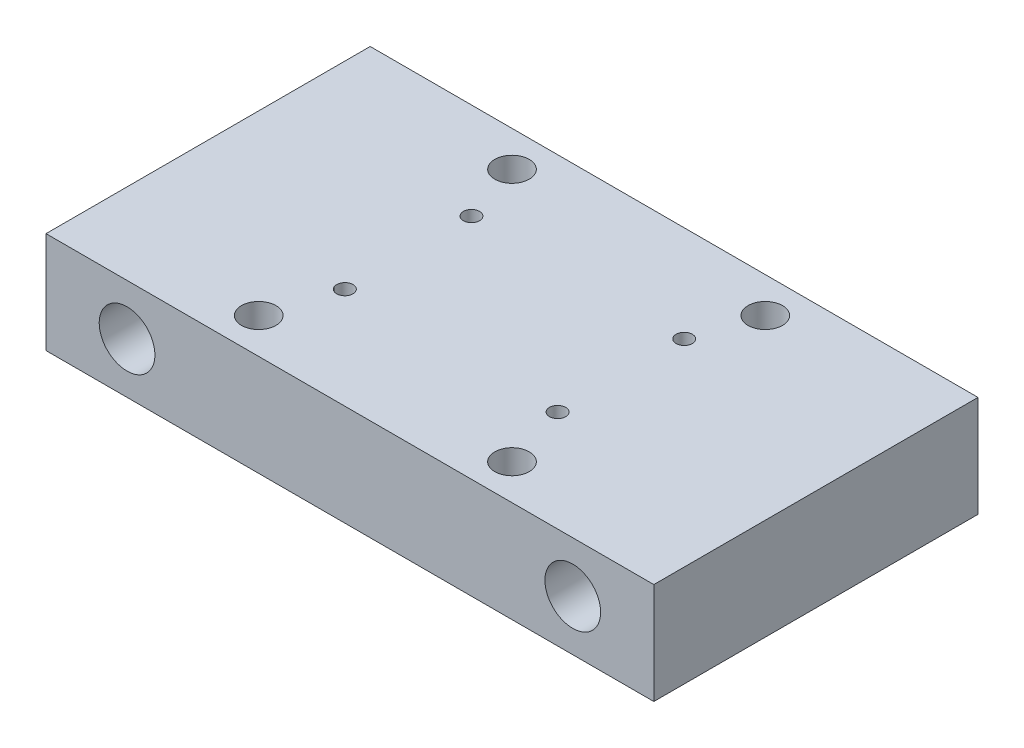
SolidWorks part; units mm, degrees
ref_plane "Front Plane" through (0, 0, 0) normal (0, 0, 1) x (1, 0, 0)
ref_plane "Top Plane" through (0, 0, 0) normal (0, 1, 0) x (1, 0, 0)
ref_plane "Right Plane" through (0, 0, 0) normal (1, 0, 0) x (0, 0, -1)
sketch "Sketch1" plane through (0, 0, 0) normal (0, 1, 0) x (1, 0, 0)
  line L1 (-12.5, 12.5) -> (12.5, 12.5)
  line L2 (-12.5, 12.5) -> (-12.5, -12.5)
  line L3 (-12.5, -12.5) -> (12.5, -12.5)
  line L4 (12.5, 12.5) -> (12.5, -12.5)
  line L5 (-12.5, 12.5) -> (12.5, -12.5) construction
  line L6 (-12.5, -12.5) -> (12.5, 12.5) construction
  line L7 (-30, 16) -> (30, 16)
  line L8 (-30, 16) -> (-30, -16)
  line L9 (-30, -16) -> (30, -16)
  line L10 (30, 16) -> (30, -16)
  line L11 (-30, 16) -> (30, -16) construction
  line L12 (-30, -16) -> (30, 16) construction
  point P0 (0, 0)
  point P6 (0, 0)
  dimension "D1" = 25
  dimension "D2" = 32
  dimension "D3" = 60
sketch "Sketch2" plane through (0, 0, 0) normal (0, 1, 0) x (1, 0, 0)
  line L0 (-30, 16) -> (30, 16) construction
  line L1 (30, 16) -> (30, -16) construction
  line L2 (-30, -16) -> (30, -16) construction
  line L3 (-30, 16) -> (-30, -16) construction
  line L4 (-30, 16) -> (30, 16)
  line L5 (30, 16) -> (30, -16)
  line L6 (-30, -16) -> (30, -16)
  line L7 (-30, 16) -> (-30, -16)
extrude "Boss-Extrude1" add sketch "Sketch2" along normal blind 10
hole_wizard "CBORE for M3 SHCS1" positions "Sketch3" profile "Sketch4" counterbore size "M3" standard "ANSI Metric" end condition through all
sketch "Sketch3" plane through (0, 0, 0) normal (0, -1, 0) x (-1, 0, 0)
  point P0 (12.5, 12.5)
  point P2 (12.5, -12.5)
  point P5 (-12.5, -12.5)
  point P8 (-12.5, 12.5)
sketch "Sketch4" plane through (-12.5, 0, -12.5) normal (1, 0, 0) x (0, 0, -1)
  line L0 (0, 0) -> (0, 10)
  line L1 (0, 10) -> (1.7, 10)
  line L3 (1.7, 10) -> (1.7, 5)
  line L4 (1.7, 5) -> (3.25, 5)
  line L5 (3.25, 5) -> (3.25, 0)
  line L7 (3.25, 0) -> (0, 0)
  line L11 (0, -6.35) -> (0, 107.95) construction
  dimension "Thru Hole Dia." = 3.4
  dimension "Thru Hole Depth" = 10
  dimension "C'Bore Dia." = 6.5
  dimension "C'Bore Depth" = 5
sketch "Sketch6" plane through (0, 0, 0) normal (0, -1, 0) x (-1, 0, 0)
  line L1 (8.5, 4) -> (-8.5, 4)
  line L2 (8.5, 4) -> (8.5, 16)
  line L3 (8.5, 16) -> (-8.5, 16)
  line L4 (-8.5, 4) -> (-8.5, 16)
  line L5 (30, 16) -> (-30, 16) construction
  line L6 (0, 0) -> (0, 4) construction
  point P4 (8.5, 3.216)
  dimension "D1" = 17
  dimension "D2" = 12
extrude "Cut-Extrude2" cut sketch "Sketch6" against normal blind 2
sketch "Sketch8" plane through (0, 0, -16) normal (0, 0, -1) x (-1, 0, 0)
  line L0 (30, 5) -> (-30, 5) construction
  line L1 (30, 10) -> (30, 0) construction
  line L2 (-30, 10) -> (-30, 0) construction
  line L4 (17.2657, 5) -> (19.6329, 0.9)
  line L5 (19.6329, 0.9) -> (24.3671, 0.9)
  line L6 (24.3671, 0.9) -> (26.7343, 5)
  line L7 (26.7343, 5) -> (24.3671, 9.1)
  line L8 (24.3671, 9.1) -> (19.6329, 9.1)
  line L9 (19.6329, 9.1) -> (17.2657, 5)
  line L10 (-17.2657, 5) -> (-19.6329, 9.1)
  line L11 (-19.6329, 9.1) -> (-24.3671, 9.1)
  line L12 (-24.3671, 9.1) -> (-26.7343, 5)
  line L13 (-26.7343, 5) -> (-24.3671, 0.9)
  line L14 (-24.3671, 0.9) -> (-19.6329, 0.9)
  line L15 (-19.6329, 0.9) -> (-17.2657, 5)
  circle A0 centre (22, 5) radius 4.1 construction
  circle A1 centre (-22, 5) radius 4.1 construction
  dimension "D1" = 8.2
  dimension "D2" = 8
  dimension "D3" = 8
extrude "Cut-Extrude4" cut sketch "Sketch8" against normal blind 5
hole_wizard "M5 Clearance Hole1" positions "Sketch10" profile "Sketch11" hole size "M5" standard "ANSI Metric" end condition through all
sketch "Sketch10" plane through (0, 0, -11) normal (0, 0, -1) x (-1, 0, 0)
  line L0 (19.6329, 0.9) -> (24.3671, 9.1)
  line L2 (-19.6329, 9.1) -> (-24.3671, 0.9)
  point P0 (22, 5)
  point P2 (-22, 5)
sketch "Sketch11" plane through (-22, 5, -11) normal (1, 0, 0) x (0, 1, 0)
  line L0 (0, 0) -> (0, 27)
  line L1 (0, 27) -> (2.75, 27)
  line L2 (2.75, 27) -> (2.75, 0)
  line L5 (2.75, 0) -> (0, 0)
  line L11 (0, -6.35) -> (0, 107.95) construction
  dimension "Thru Hole Dia." = 5.5
  dimension "Thru Hole Depth" = 27
sketch "Sketch12" plane through (0, 0, 0) normal (0, -1, 0) x (1, 0, 0)
  line L0 (-8.5, -16) -> (-30, -16) construction
  line L1 (12.5, -16) -> (-12.5, -16) construction
  line L2 (12.5, -16) -> (12.5, 8) construction
  line L3 (12.5, 8) -> (-12.5, 8) construction
  line L4 (-12.5, -16) -> (-12.5, 8) construction
  line L7 (10.5, -6.5) -> (-10.5, -6.5) construction
  line L8 (10.5, -6.5) -> (10.5, 6) construction
  line L9 (10.5, 6) -> (-10.5, 6) construction
  line L10 (-10.5, -6.5) -> (-10.5, 6) construction
  line L11 (10.5, -6.5) -> (-10.5, 6) construction
  line L12 (10.5, 6) -> (-10.5, -6.5) construction
  circle A0 centre (10.5, -6.5) radius 2
  circle A1 centre (-10.5, -6.5) radius 2
  circle A2 centre (10.5, 6) radius 2
  circle A3 centre (-10.5, 6) radius 2
  point P6 (0, -0.25)
  dimension "D1" = 24
  dimension "D2" = 25
  dimension "D3" = 2
  dimension "D4" = 12.5
  dimension "D5" = 21
extrude "Boss-Extrude2" add sketch "Sketch12" along normal blind 2.5
hole_wizard "M2x0.4 Tapped Hole1" positions "Sketch13" profile "Sketch14" tap size "M2x0.4" standard "ANSI Metric" end condition through all
sketch "Sketch13" plane through (0, -2.5, 0) normal (0, -1, 0) x (-1, 0, 0)
  circle A0 centre (10.5, 6.5) radius 2 construction
  circle A1 centre (-10.5, -6) radius 2 construction
  point P0 (-10.5, -6)
  point P2 (-10.5, 6.5)
  point P5 (10.5, -6)
  point P8 (10.5, 6.5)
  point P11 (11.6097, 7.1524)
  point P16 (0, 0)
sketch "Sketch14" plane through (10.5, -2.5, 6) normal (1, 0, 0) x (0, 0, -1)
  line L0 (0, 0) -> (0, 12.5)
  line L1 (0, 12.5) -> (0.8, 12.5)
  line L2 (0.8, 12.5) -> (0.8, 0)
  line L5 (0.8, 0) -> (0, 0)
  line L11 (0, -6.35) -> (0, 107.95) construction
  dimension "Thru Tap Drill Dia." = 1.6
  dimension "Thru Tap Drill Depth" = 12.5
cosmetic thread "Hole Thread1" parameters "D2"=2
cosmetic thread "Hole Thread2" parameters "D2"=2
cosmetic thread "Hole Thread3" parameters "D2"=2
cosmetic thread "Hole Thread4" parameters "D2"=2
